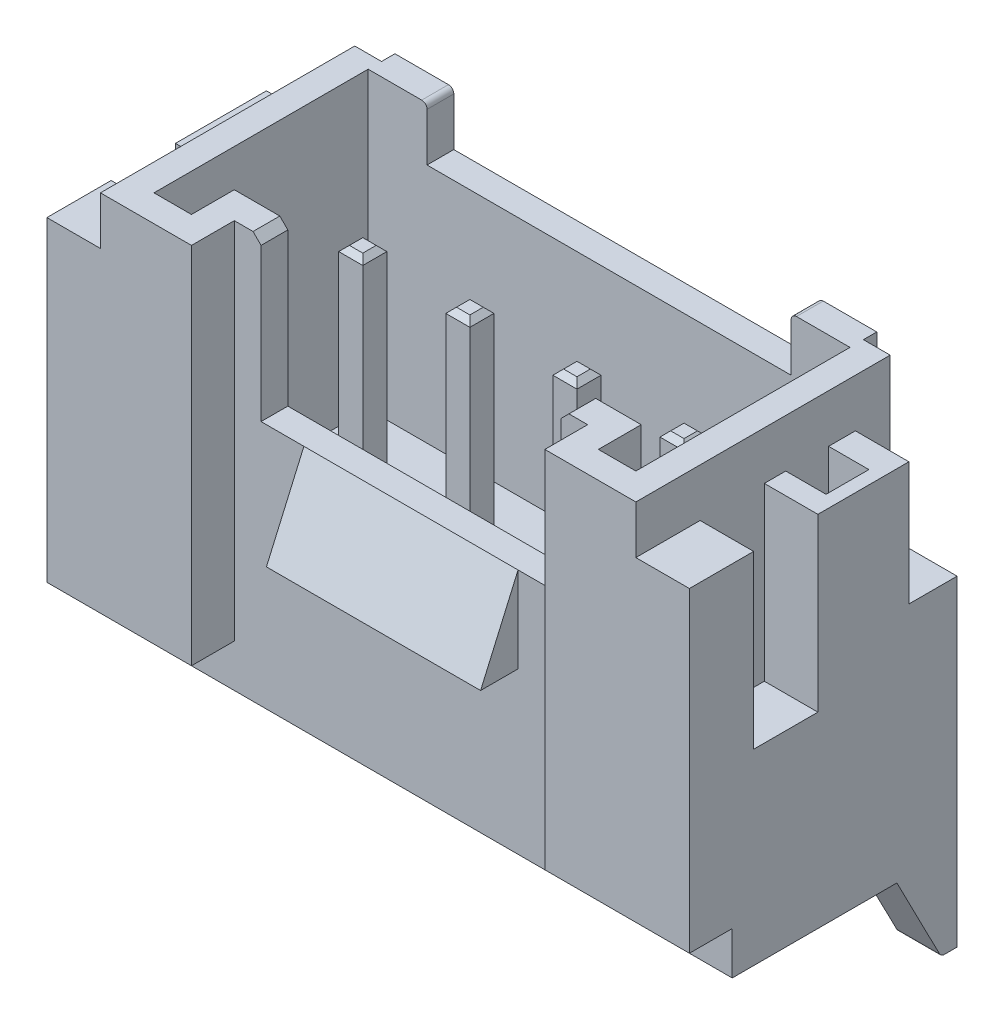
SolidWorks part; units mm, degrees
ref_plane "Plan de face" through (0, 0, 0) normal (0, 0, 1) x (1, 0, 0)
ref_plane "Plan de dessus" through (0, 0, 0) normal (0, 1, 0) x (1, 0, 0)
ref_plane "Plan de droite" through (0, 0, 0) normal (1, 0, 0) x (0, 0, -1)
sketch "Esquisse1" plane through (0, 0, 0) normal (0, 1, 0) x (1, 0, 0)
  line L1 (0, 0) -> (10, 0)
  line L2 (0, 0) -> (0, 5)
  line L3 (0, 5) -> (10, 5)
  line L4 (10, 0) -> (10, 5)
  dimension "D1" = 5
  dimension "D2" = 10
extrude "Boss.-Extru.1" add sketch "Esquisse1" along normal blind 7.6
sketch "Esquisse2" plane through (0, 7.6, 0) normal (0, 1, 0) x (1, 0, 0)
  line L0 (0, 0) -> (10, 0) construction
  line L1 (1.7, 0) -> (8.3, 0)
  line L2 (1.7, 0) -> (1.7, 0.8)
  line L3 (1.7, 0.8) -> (8.3, 0.8)
  line L4 (8.3, 0) -> (8.3, 0.8)
  line L5 (0, 5) -> (0, 0) construction
  line L6 (10, 0) -> (10, 5) construction
  dimension "D1" = 1.7
  dimension "D2" = 1.7
  dimension "D3" = 0.8
extrude "Enlèv. mat.-Extru.1" cut sketch "Esquisse2" against normal blind 8
sketch "Esquisse4" plane through (0, 7.6, 0) normal (0, 1, 0) x (1, 0, 0)
  line L16 (0.5, 0.5) -> (1.2, 0.5)
  line L17 (1.2, 0.5) -> (1.2, 1.3)
  line L18 (1.2, 1.3) -> (8.8, 1.3)
  line L19 (8.8, 1.3) -> (8.8, 0.5)
  line L20 (8.8, 0.5) -> (9.5, 0.5)
  line L21 (9.5, 0.5) -> (9.5, 4.5)
  line L22 (9.5, 4.5) -> (0.5, 4.5)
  line L23 (0.5, 4.5) -> (0.5, 0.5)
  line L24 (0.5, 0.5) -> (1.2, 0.5)
  line L25 (1.2, 0.5) -> (1.2, 1.3)
  line L26 (1.2, 1.3) -> (8.8, 1.3)
  line L27 (8.8, 1.3) -> (8.8, 0.5)
  line L28 (8.8, 0.5) -> (9.5, 0.5)
  line L29 (9.5, 0.5) -> (9.5, 4.5)
  line L30 (9.5, 4.5) -> (0.5, 4.5)
  line L31 (0.5, 4.5) -> (0.5, 0.5)
  dimension "D1" = 0.5
extrude "Enlèv. mat.-Extru.2" cut sketch "Esquisse4" against normal blind 5.5
sketch "Esquisse5" plane through (0, 7.6, 0) normal (0, 1, 0) x (1, 0, 0)
  line L0 (10, 5) -> (0, 5) construction
  line L1 (1.6, 5) -> (8.4, 5)
  line L2 (1.6, 5) -> (1.6, 4.5)
  line L3 (1.6, 4.5) -> (8.4, 4.5)
  line L4 (8.4, 5) -> (8.4, 4.5)
  line L5 (9.5, 4.5) -> (0.5, 4.5) construction
  line L6 (10, 0) -> (10, 5) construction
  line L7 (0, 5) -> (0, 0) construction
  dimension "D1" = 1.6
  dimension "D2" = 1.6
extrude "Enlèv. mat.-Extru.3" cut sketch "Esquisse5" against normal blind 1
sketch "Esquisse6" plane through (0, 7.6, 0) normal (0, 1, 0) x (1, 0, 0)
  line L0 (1.2, 1.3) -> (8.8, 1.3) construction
  line L1 (2.2, 1.3) -> (7.8, 1.3)
  line L2 (2.2, 1.3) -> (2.2, 0.8)
  line L3 (2.2, 0.8) -> (7.8, 0.8)
  line L4 (7.8, 1.3) -> (7.8, 0.8)
  line L5 (8.3, 0.8) -> (1.7, 0.8) construction
  line L6 (10, 0) -> (10, 5) construction
  line L7 (0, 5) -> (0, 0) construction
  dimension "D1" = 2.2
  dimension "D2" = 2.2
extrude "Enlèv. mat.-Extru.4" cut sketch "Esquisse6" against normal blind 3
sketch "Esquisse8" plane through (0, 0, 0) normal (0, -1, 0) x (1, 0, 0)
  line L0 (8.3, -0.8) -> (1.7, -0.8) construction
  line L1 (1.7, -0.8) -> (8.3, -0.8)
  line L2 (1.7, -0.8) -> (1.7, -5)
  line L3 (1.7, -5) -> (8.3, -5)
  line L4 (8.3, -0.8) -> (8.3, -5)
  line L5 (10, -5) -> (0, -5) construction
  line L6 (0, -5) -> (0, 0) construction
  line L7 (10, 0) -> (10, -5) construction
  dimension "D1" = 1.7
  dimension "D2" = 1.7
extrude "Enlèv. mat.-Extru.6" cut sketch "Esquisse8" against normal blind 0.9
sketch "Esquisse9" plane through (1.7, 0, 0) normal (1, 0, 0) x (0, 0, -1)
  line L1 (4.7101, 0.9771) -> (3.4, 0)
  line L2 (3.4, 0) -> (2.4, 0)
  line L3 (2.4, 0) -> (1.0899, 0.9771)
  line L5 (4.7101, 0.9771) -> (1.0899, 0.9771)
  line L6 (5, 0.9) -> (0.8, 0.9) construction
  line L7 (2.9, 0) -> (2.9, 0.9771) construction
  dimension "D2" = 1
  dimension "D4" = 0.3
  dimension "D5" = 0.3
extrude "Boss.-Extru.2" add sketch "Esquisse9" along normal blind 6.8
ref_plane "Plan1" through (5, 0, 0) normal (1, 0, 0) x (0, 0, -1)
sketch "Esquisse11" plane through (5, 0, 0) normal (1, 0, 0) x (0, 0, -1)
  line L0 (0.8, 4.6) -> (0.1, 3)
  line L1 (0.1, 3) -> (0.8, 3)
  line L2 (0.8, 0.9) -> (0.8, 7.6) construction
  line L3 (0.8, 3) -> (0.8, 4.6)
  dimension "D1" = 1.6
  dimension "D2" = 0.7
extrude "Boss.-Extru.3" add sketch "Esquisse11" along normal blind 2 and the other way blind 2
ref_plane "Plan2" through (0, 1, 0) normal (0, 1, 0) x (1, 0, 0)
sketch "Esquisse17" plane through (0, 1, 0) normal (0, 1, 0) x (1, 0, 0)
  line L0 (3.035, 0.8) -> (3.035, 5) construction
  line L1 (5, 0.8) -> (5, 5) construction
  line L2 (6.965, 0.8) -> (6.965, 5) construction
  line L4 (1.7, 0.8) -> (1.7, 5) construction
  line L8 (2.41, 0.8) -> (3.66, 0.8)
  line L9 (3.66, 0.8) -> (3.66, 5)
  line L10 (3.66, 5) -> (2.41, 5)
  line L11 (2.41, 5) -> (2.41, 0.8)
  line L16 (4.375, 0.8) -> (5.625, 0.8)
  line L17 (5.625, 0.8) -> (5.625, 5)
  line L18 (5.625, 5) -> (4.375, 5)
  line L19 (4.375, 5) -> (4.375, 0.8)
  line L24 (6.34, 0.8) -> (7.59, 0.8)
  line L25 (7.59, 0.8) -> (7.59, 5)
  line L26 (7.59, 5) -> (6.34, 5)
  line L27 (6.34, 5) -> (6.34, 0.8)
  dimension "D1" = 1.25
  dimension "D2" = 1.25
  dimension "D3" = 1.25
  dimension "D4" = 3.3
  dimension "D5" = 1.34
  dimension "D6" = 1.34
extrude "Boss.-Extru.8" add sketch "Esquisse17" against normal blind 1
chamfer "Chanfrein1" distance 0.15 angle 45 2 edges at (2.2, 7.6, -1.05) (7.8, 7.6, -1.05)
sketch "Esquisse13" plane through (0, 0, 0) normal (0, -1, 0) x (1, 0, 0)
  line L0 (5, -0.8) -> (5, -5) construction
  line L1 (4.225, -2.9) -> (1.775, -2.9) construction
  line L2 (4.225, -3.125) -> (3.775, -3.125)
  line L3 (4.225, -3.125) -> (4.225, -2.675)
  line L4 (4.225, -2.675) -> (3.775, -2.675)
  line L5 (3.775, -3.125) -> (3.775, -2.675)
  line L6 (2.225, -3.125) -> (1.775, -3.125)
  line L7 (2.225, -3.125) -> (2.225, -2.675)
  line L8 (2.225, -2.675) -> (1.775, -2.675)
  line L9 (1.775, -3.125) -> (1.775, -2.675)
  line L10 (4.375, -2.4) -> (3.66, -2.4) construction
  line L11 (2.41, -0.8) -> (3.66, -0.8) construction
  line L12 (8.225, -3.125) -> (8.225, -2.675)
  line L13 (7.775, -2.675) -> (8.225, -2.675)
  line L14 (7.775, -3.125) -> (7.775, -2.675)
  line L15 (7.775, -3.125) -> (8.225, -3.125)
  line L16 (6.225, -3.125) -> (6.225, -2.675)
  line L17 (5.775, -2.675) -> (6.225, -2.675)
  line L18 (5.775, -3.125) -> (5.775, -2.675)
  line L19 (5.775, -3.125) -> (6.225, -3.125)
  line L20 (4.375, -0.8) -> (5.625, -0.8) construction
  point P14 (3.035, -0.8)
  dimension "D1" = 0.45
  dimension "D2" = 0.5
  dimension "D3" = 2
  dimension "D4" = 2
extrude "Boss.-Extru.5" add sketch "Esquisse13" along normal blind 0.45 and the other way blind 6.3
sketch "Esquisse18" plane through (0, 0.9, 0) normal (0, -1, 0) x (1, 0, 0)
  line L1 (1.7, -0.8) -> (2.41, -0.8)
  line L2 (1.7, -0.8) -> (1.7, -1.1933)
  line L3 (1.7, -1.1933) -> (2.41, -1.1933)
  line L4 (2.41, -0.8) -> (2.41, -1.1933)
  line L5 (3.66, -0.8) -> (4.375, -0.8)
  line L6 (3.66, -0.8) -> (3.66, -1.1933)
  line L7 (3.66, -1.1933) -> (4.375, -1.1933)
  line L8 (4.375, -0.8) -> (4.375, -1.1933)
  line L9 (5.625, -0.8) -> (6.34, -0.8)
  line L10 (5.625, -0.8) -> (5.625, -1.1933)
  line L11 (5.625, -1.1933) -> (6.34, -1.1933)
  line L12 (6.34, -0.8) -> (6.34, -1.1933)
  line L13 (7.59, -0.8) -> (8.3, -0.8)
  line L14 (7.59, -0.8) -> (7.59, -1.1933)
  line L15 (7.59, -1.1933) -> (8.3, -1.1933)
  line L16 (8.3, -0.8) -> (8.3, -1.1933)
extrude "Boss.-Extru.9" add sketch "Esquisse18" along normal blind 0.9
chamfer "Chanfrein2" distance 0.1 angle 45 16 edges at (2, 6.3, -2.675) (4.225, 6.3, -2.9) (4, 6.3, -2.675) (3.775, 6.3, -2.9) (8.225, 6.3, -2.9) (8, 6.3, -2.675) (7.775, 6.3, -2.9) (8, 6.3, -3.125) (6.225, 6.3, -2.9) (6, 6.3, -2.675) (5.775, 6.3, -2.9) (6, 6.3, -3.125) (4, 6.3, -3.125) (1.775, 6.3, -2.9) (2, 6.3, -3.125) (2.225, 6.3, -2.9)
sketch "Esquisse14" plane through (0, 0, -3.125) normal (0, 0, -1) x (-1, 0, 0)
  line L1 (-8.225, -0.45) -> (-7.775, -0.45)
  line L2 (-8.225, -0.45) -> (-8.225, -0.02)
  line L3 (-8.225, -0.02) -> (-7.775, -0.02)
  line L4 (-7.775, -0.45) -> (-7.775, -0.02)
  line L9 (-6.225, -0.45) -> (-5.775, -0.45)
  line L10 (-6.225, -0.45) -> (-6.225, -0.02)
  line L11 (-6.225, -0.02) -> (-5.775, -0.02)
  line L12 (-5.775, -0.45) -> (-5.775, -0.02)
  line L13 (-4.225, -0.45) -> (-3.775, -0.45)
  line L14 (-4.225, -0.45) -> (-4.225, -0.02)
  line L15 (-4.225, -0.02) -> (-3.775, -0.02)
  line L16 (-3.775, -0.45) -> (-3.775, -0.02)
  line L17 (-2.225, -0.45) -> (-1.775, -0.45)
  line L18 (-2.225, -0.45) -> (-2.225, -0.02)
  line L19 (-2.225, -0.02) -> (-1.775, -0.02)
  line L20 (-1.775, -0.45) -> (-1.775, -0.02)
  line L22 (-8.225, 0) -> (-8.225, -0.45) construction
  dimension "D1" = 0.43
  dimension "D2" = 4
extrude "Boss.-Extru.6" add sketch "Esquisse14" along normal blind 1.875
fillet "Congé1" radius 0.1 8 edges at (4, -0.02, -3.125) (6, -0.02, -3.125) (8, -0.02, -3.125) (8, -0.45, -2.675) (6, -0.45, -2.675) (4, -0.45, -2.675) (2, -0.02, -3.125) (2, -0.45, -2.675)
fillet "Congé2" radius 0.1 2 edges at (8.4, 7.6, -4.75) (1.6, 7.6, -4.75)
ref_plane "Plan3" through (0, 6.7, 0) normal (0, 1, 0) x (1, 0, 0)
sketch "Esquisse21" plane through (0, 6.7, 0) normal (0, 1, 0) x (1, 0, 0)
  line L1 (0, 5) -> (-1, 5)
  line L2 (0, 5) -> (0, 0)
  line L3 (0, 0) -> (-1, 0)
  line L4 (-1, 5) -> (-1, 0)
  line L5 (10, 5) -> (11, 5)
  line L6 (10, 5) -> (10, 0)
  line L7 (10, 0) -> (11, 0)
  line L8 (11, 5) -> (11, 0)
  dimension "D1" = 1
  dimension "D2" = 1
extrude "Boss.-Extru.10" add sketch "Esquisse21" against normal blind 6.7
sketch "Esquisse22" plane through (11, 0, 0) normal (1, 0, 0) x (0, 0, -1)
  line L1 (0, 0) -> (0.8, 0)
  line L2 (0, 0) -> (0, 0.8)
  line L3 (0, 0.8) -> (0.8, 0.8)
  line L4 (0.8, 0) -> (0.8, 0.8)
  dimension "D1" = 0.8
  dimension "D2" = 0.8
extrude "Enlèv. mat.-Extru.8" cut sketch "Esquisse22" against normal blind 12
sketch "Esquisse23" plane through (0, 6.7, 0) normal (0, 1, 0) x (1, 0, 0)
  line L0 (5, 5) -> (5, 0.1) construction
  line L1 (10, 5) -> (10, 0) construction
  line L2 (11, 5) -> (10, 5)
  line L3 (11, 5) -> (11, 4.1)
  line L4 (11, 4.1) -> (10, 4.1)
  line L5 (10, 4.75) -> (10, 4.1)
  line L6 (8.4, 5) -> (1.6, 5) construction
  line L7 (10.7525, 3.6) -> (10, 3.6)
  line L8 (10.7525, 3.6) -> (10.7525, 2.8)
  line L9 (10.7525, 2.8) -> (10, 2.8)
  line L10 (10, 3.6) -> (10, 2.8)
  line L11 (10, 5) -> (9.5, 5)
  line L12 (-0.7525, 2.8) -> (0, 2.8)
  line L13 (10, 4.75) -> (9.5, 4.75)
  line L14 (9.5, 5) -> (9.5, 4.75)
  line L15 (3, 0.1) -> (7, 0.1) construction
  line L16 (-0.7525, 3.6) -> (-0.7525, 2.8)
  line L17 (0, 3.6) -> (0, 2.8)
  line L18 (-0.7525, 3.6) -> (0, 3.6)
  line L19 (0, 4.75) -> (0, 4.1)
  line L20 (-1, 4.1) -> (0, 4.1)
  line L21 (-1, 5) -> (-1, 4.1)
  line L22 (-1, 5) -> (0, 5)
  line L23 (0, 5) -> (0.5, 5)
  line L24 (0.5, 5) -> (0.5, 4.75)
  line L25 (0, 4.75) -> (0.5, 4.75)
  dimension "D1" = 0.5
  dimension "D2" = 0.25
  dimension "D3" = 0.9
  dimension "D4" = 2.2
  dimension "D5" = 1.4
extrude "Enlèv. mat.-Extru.9" cut sketch "Esquisse23" against normal blind 2.3 and the other way blind 0.9
sketch "Esquisse24" plane through (0, 6.7, 0) normal (0, 1, 0) x (1, 0, 0)
  line L0 (10, 2.8) -> (10, 0) construction
  line L1 (10, 1.2) -> (11, 1.2)
  line L2 (10, 1.2) -> (10, 2.4)
  line L3 (10, 2.4) -> (11, 2.4)
  line L4 (11, 1.2) -> (11, 2.4)
  line L5 (11, 0) -> (11, 4.1) construction
  line L6 (10, 0) -> (11, 0) construction
  line L7 (5, 5) -> (5, 0.1) construction
  line L8 (8.4, 5) -> (1.6, 5) construction
  line L9 (3, 0.1) -> (7, 0.1) construction
  line L10 (0, 1.2) -> (0, 2.4)
  line L11 (0, 1.2) -> (-1, 1.2)
  line L12 (-1, 1.2) -> (-1, 2.4)
  line L13 (0, 2.4) -> (-1, 2.4)
  dimension "D1" = 1.2
  dimension "D2" = 1.2
extrude "Enlèv. mat.-Extru.10" cut sketch "Esquisse24" against normal blind 3.2
sketch "Esquisse25" plane through (0, -0.45, 0) normal (0, -1, 0) x (1, 0, 0)
  line L1 (8.225, -5) -> (8.225, -2.775) construction
  line L2 (7.775, -5) -> (8.225, -5)
  line L3 (7.775, -5) -> (7.775, -4.55)
  line L4 (7.775, -4.55) -> (8.225, -4.55)
  line L5 (8.225, -5) -> (8.225, -4.55)
  line L6 (5.775, -5) -> (5.775, -4.55)
  line L7 (5.775, -4.55) -> (6.225, -4.55)
  line L8 (6.225, -5) -> (6.225, -4.55)
  line L9 (5.775, -5) -> (6.225, -5)
  line L10 (3.775, -5) -> (3.775, -4.55)
  line L11 (3.775, -4.55) -> (4.225, -4.55)
  line L12 (4.225, -5) -> (4.225, -4.55)
  line L13 (3.775, -5) -> (4.225, -5)
  line L14 (1.775, -5) -> (1.775, -4.55)
  line L15 (1.775, -4.55) -> (2.225, -4.55)
  line L16 (2.225, -5) -> (2.225, -4.55)
  line L17 (1.775, -5) -> (2.225, -5)
  dimension "D1" = 0.45
  dimension "D2" = 4
extrude "Boss.-Extru.11" add sketch "Esquisse25" along normal blind 1.9
fillet "Congé3" radius 0.1 8 edges at (8, -0.02, -5) (8, -0.45, -4.55) (6, -0.02, -5) (6, -0.45, -4.55) (4, -0.45, -4.55) (4, -0.02, -5) (2, -0.02, -5) (2, -0.45, -4.55)
fillet "Congé4" radius 0.2 4 edges at (8, -2.35, -4.55) (6, -2.35, -4.55) (4, -2.35, -4.55) (2, -2.35, -4.55)
sketch "Esquisse27" plane through (-1, 0, 0) normal (-1, 0, 0) x (0, 0, 1)
  line L0 (-5, 0) -> (-5, -2.5474) construction
  line L1 (-5, -2.5474) -> (500000, -0.784) construction
  line L2 (-5, 0) -> (-5, -1.6)
  line L3 (-5, -1.6) -> (-4.761, -1.6)
  line L4 (-4.6721, -1.5458) -> (-3.8754, 0)
  line L5 (-5, 0) -> (-0.8, 0) construction
  line L6 (-3.8754, 0) -> (-5, 0)
  arc A0 (-4.761, -1.6) -> (-4.6721, -1.5458) centre (-4.761, -1.5) ccw
  point P11 (-4.7, -1.6)
  dimension "D4" = 0.1
  dimension "D1" = 1.6
  dimension "D2" = 0.3
  dimension "D3" = 1.8
extrude "Boss.-Extru.12" add sketch "Esquisse27" against normal blind 0.8
sketch "Esquisse28" plane through (11, 0, 0) normal (1, 0, 0) x (0, 0, -1)
  line L4 (5, -1.6) -> (5, 0)
  line L5 (4.761, -1.6) -> (5, -1.6)
  line L6 (3.8754, 0) -> (4.6721, -1.5458)
  line L7 (5, 0) -> (3.8754, 0)
  line L8 (5, -1.6) -> (5, 0)
  line L9 (4.761, -1.6) -> (5, -1.6)
  line L10 (3.8754, 0) -> (4.6721, -1.5458)
  line L11 (5, 0) -> (3.8754, 0)
  arc A1 (4.6721, -1.5458) -> (4.761, -1.6) centre (4.761, -1.5) ccw
  arc A2 (4.6721, -1.5458) -> (4.761, -1.6) centre (4.761, -1.5) ccw
  dimension "D1" = 0
extrude "Boss.-Extru.13" add sketch "Esquisse28" against normal blind 0.8
